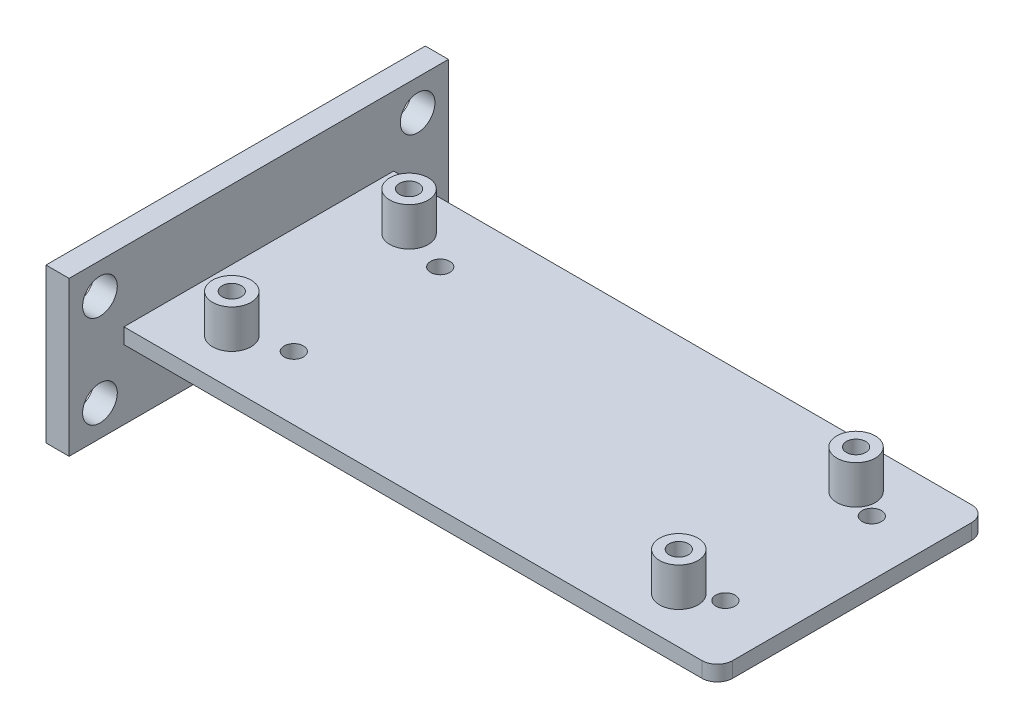
SolidWorks part; units mm, degrees
material "ABS"
ref_plane "Спереди" through (0, 0, 0) normal (0, 0, 1) x (1, 0, 0)
ref_plane "Сверху" through (0, 0, 0) normal (0, 1, 0) x (1, 0, 0)
ref_plane "Справа" through (0, 0, 0) normal (1, 0, 0) x (0, 0, -1)
sketch "Эскиз1" plane through (0, 0, 0) normal (0, 1, 0) x (1, 0, 0)
  line L1 (0, 0) -> (80, 0)
  line L2 (0, 0) -> (0, -35)
  line L3 (0, -35) -> (80, -35)
  line L4 (80, 0) -> (80, -35)
  dimension "D1" = 80
  dimension "D2" = 35
extrude "Бобышка-Вытянуть1" add sketch "Эскиз1" along normal blind 2
sketch "Эскиз2" plane through (0, 2, 0) normal (0, 1, 0) x (1, 0, 0)
  line L0 (0, 0) -> (0, -35) construction
  line L1 (80, -35) -> (80, 0) construction
  line L2 (80, 0) -> (0, 0) construction
  line L3 (0, -35) -> (80, -35) construction
  circle A0 centre (11, -6) radius 2.5
  circle A1 centre (11, -29) radius 2.5
  circle A2 centre (69, -6) radius 2.5
  circle A3 centre (69, -29) radius 2.5
  dimension "D1" = 11
  dimension "D2" = 11
  dimension "D3" = 11
  dimension "D4" = 11
  dimension "D5" = 6
  dimension "D6" = 6
  dimension "D7" = 5
  dimension "D8" = 6
  dimension "D9" = 6
  dimension "D10" = 5
  dimension "D11" = 5
  dimension "D12" = 5
extrude "Бобышка-Вытянуть2" add sketch "Эскиз2" along normal blind 5
sketch "Эскиз3" plane through (0, 7, 0) normal (0, 1, 0) x (1, 0, 0)
  circle A0 centre (11, -6) radius 1.25
  circle A1 centre (11, -29) radius 1.25
  circle A2 centre (69, -6) radius 1.25
  circle A3 centre (69, -29) radius 1.25
  dimension "D1" = 2.5
  dimension "D2" = 2.5
  dimension "D3" = 2.5
  dimension "D4" = 2.5
extrude "Вырез-Вытянуть1" cut sketch "Эскиз3" against normal through all both and the other way through all
sketch "Эскиз4" plane through (0, 2, 0) normal (0, 1, 0) x (1, 0, 0)
  line L0 (0, -17.5) -> (80, -17.5) construction
  line L1 (0, 0) -> (0, -35) construction
  line L2 (80, -35) -> (80, 0) construction
  circle A0 centre (4, -17.5) radius 2
  circle A1 centre (76, -17.5) radius 2
  dimension "D2" = 4
  dimension "D3" = 4
  dimension "D4" = 4
  dimension "D1" = 4
extrude "Вырез-Вытянуть2" [suppressed] cut sketch "Эскиз4" against normal through all
fillet "Скругление1" radius 2 1 edges at (0, 1, 0) type face fillet first side face at (0, 1, 17.5) second side face at (40, 1, 0)
fillet "Скругление2" radius 2 1 edges at (0, 1, 35) type face fillet first side face at (0, 1, 18.5) second side face at (40, 1, 35)
fillet "Скругление3" radius 2 1 edges at (80, 1, 35) type face fillet first side face at (41, 1, 35) second side face at (80, 1, 17.5)
fillet "Скругление4" radius 2 1 edges at (80, 1, 0) type face fillet first side face at (41, 1, 0) second side face at (80, 1, 16.5)
sketch "Эскиз5" plane through (0, 0, 0) normal (0, -1, 0) x (1, 0, 0)
  circle A0 centre (16.7893, 26.746) radius 1.25
  circle A1 centre (72.7893, 26.746) radius 1.25
  circle A2 centre (72.7893, 7.746) radius 1.25
  circle A3 centre (16.7893, 7.746) radius 1.25
  point P2 (16.7893, 26.746)
  dimension "D1" = 2
  dimension "D2" = 2
extrude "Вырез-Вытянуть3" cut sketch "Эскиз5" against normal blind 10
sketch "Эскиз6" plane through (0, 0, 0) normal (0, -1, 0) x (1, 0, 0)
  circle A0 centre (16.7893, 26.746) radius 1.25
  circle A1 centre (16.7893, 26.746) radius 2.5
  circle A2 centre (72.7893, 26.746) radius 2.5
  circle A3 centre (72.7893, 26.746) radius 1.25
  circle A4 centre (72.7893, 7.746) radius 2.5
  circle A5 centre (72.7893, 7.746) radius 1.25
  circle A6 centre (16.7893, 7.746) radius 2.5
  circle A7 centre (16.7893, 7.746) radius 1.25
  dimension "D1" = 2
  dimension "D2" = 2
extrude "Бобышка-Вытянуть3" add sketch "Эскиз6" along normal blind 4
sketch "Эскиз7" plane through (0, 0, 0) normal (-1, 0, 0) x (0, 0, 1)
  line L0 (17.5, 2) -> (17.5, 0) construction
  line L1 (2, 2) -> (33, 2) construction
  line L2 (2, 0) -> (33, 0) construction
  line L3 (-7.1094, 1) -> (42.7824, 1) construction
  line L4 (42.1094, -9) -> (-7.1094, -9)
  line L5 (42.1094, -9) -> (42.1094, 11)
  line L6 (42.1094, 11) -> (-7.1094, 11)
  line L7 (-7.1094, -9) -> (-7.1094, 11)
  line L8 (42.1094, -9) -> (-7.1094, 11) construction
  line L9 (42.1094, 11) -> (-7.1094, -9) construction
  circle A0 centre (38.1094, -5) radius 2.25
  circle A1 centre (-3.1094, -5) radius 2.25
  circle A2 centre (-3.1094, 7) radius 2.25
  circle A3 centre (38.1094, 7) radius 2.25
  point P6 (17.5, 1)
  dimension "D1" = 4
  dimension "D2" = 4
  dimension "D3" = 20
extrude "Бобышка-Вытянуть4" add sketch "Эскиз7" against normal blind 3
